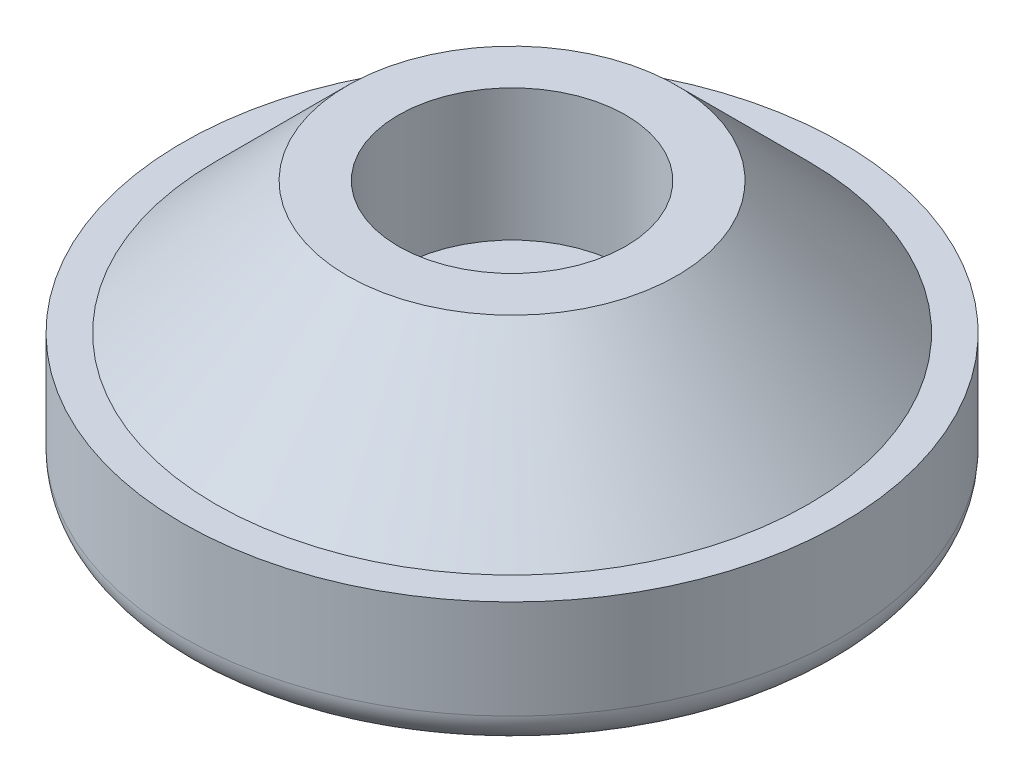
SolidWorks part; units mm, degrees
ref_plane "Plano frontal" through (0, 0, 0) normal (0, 0, 1) x (1, 0, 0)
ref_plane "Plano superior" through (0, 0, 0) normal (0, 1, 0) x (1, 0, 0)
ref_plane "Plano direito" through (0, 0, 0) normal (1, 0, 0) x (0, 0, -1)
sketch "Esboço1" plane through (0, 0, 0) normal (0, 1, 0) x (1, 0, 0)
  circle A0 centre (0, 0) radius 5
  dimension "D1" = 10
extrude "Ressalto-extrusão1" add sketch "Esboço1" along normal blind 2
sketch "Esboço2" plane through (0, 2, 0) normal (0, 1, 0) x (1, 0, 0)
  circle A0 centre (0, 0) radius 2.5
  dimension "D1" = 5
extrude "Ressalto-extrusão2" add sketch "Esboço2" along normal blind 2
sketch "Esboço3" plane through (0, 4, 0) normal (0, 1, 0) x (1, 0, 0)
  circle A0 centre (0, 0) radius 1.725
  dimension "D1" = 3.45
extrude "Corte-extrusão1" cut sketch "Esboço3" against normal blind 2
chamfer "Chanfro1" distance 2 angle 45 1 edges at (0, 2, 2.5)
fillet "Filete1" radius 0.5 1 edges at (0, 0, 5) type face fillet first side face at (0, 2, 5) second side face at (0, 0, 5)
